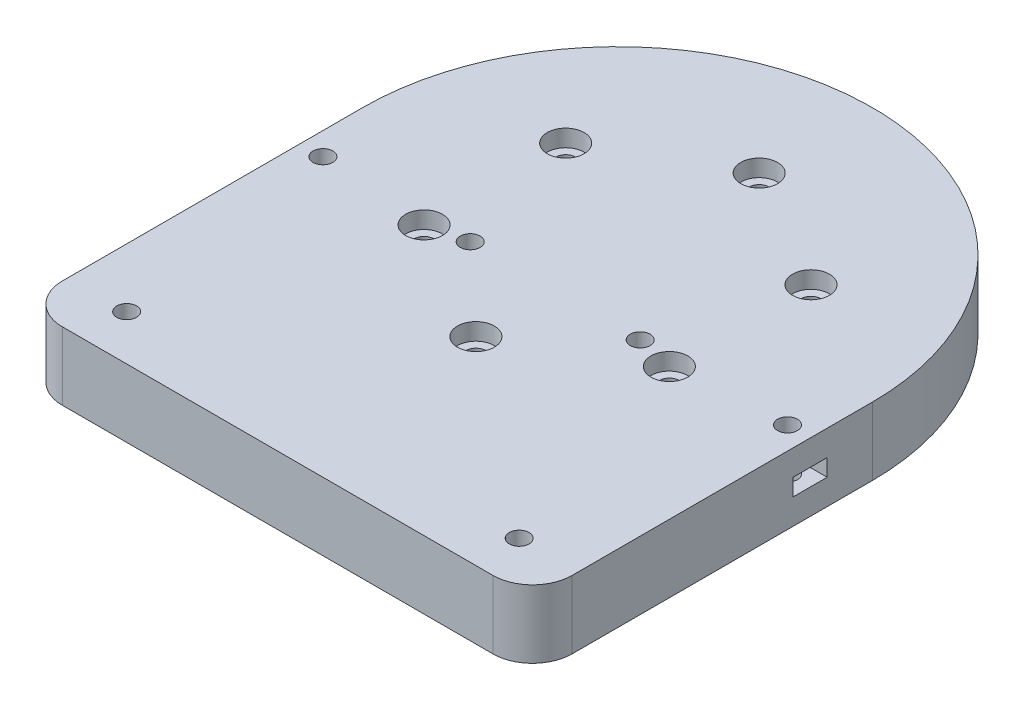
SolidWorks part; units mm, degrees
ref_plane "Front Plane" through (0, 0, 0) normal (0, 0, 1) x (1, 0, 0)
ref_plane "Top Plane" through (0, 0, 0) normal (0, 1, 0) x (1, 0, 0)
ref_plane "Right Plane" through (0, 0, 0) normal (1, 0, 0) x (0, 0, -1)
sketch "Sketch1" plane through (0, 0, 0) normal (0, 1, 0) x (1, 0, 0)
  circle A0 centre (0, 0) radius 45
  dimension "D1" = 90
extrude "Boss-Extrude1" add sketch "Sketch1" along normal blind 12
sketch "Sketch2" plane through (0, 0, 0) normal (0, -1, 0) x (1, 0, 0)
  circle A0 centre (0, 0) radius 35
  dimension "D1" = 70
extrude "Cut-Extrude1" cut sketch "Sketch2" against normal blind 6
sketch "Sketch3" plane through (0, 12, 0) normal (0, 1, 0) x (1, 0, 0)
  line L0 (0, 0) -> (0, -25) construction
  circle A0 centre (0, 0) radius 25 construction
  circle A1 centre (0, -25) radius 1.75
  circle A2 centre (-21.6506, -12.5) radius 1.75
  circle A3 centre (-21.6506, 12.5) radius 1.75
  circle A4 centre (0, 25) radius 1.75
  circle A5 centre (21.6506, 12.5) radius 1.75
  circle A6 centre (21.6506, -12.5) radius 1.75
  point P17 (0, 0)
  dimension "D1" = 50
  dimension "D2" = 3.5
  dimension "D3" = 6
extrude "Cut-Extrude2" cut sketch "Sketch3" against normal through all
sketch "Sketch4" plane through (0, 12, 0) normal (0, 1, 0) x (1, 0, 0)
  circle A0 centre (0, 25) radius 3.25
  circle A1 centre (21.6506, 12.5) radius 3.25
  circle A2 centre (21.6506, -12.5) radius 3.25
  circle A3 centre (0, -25) radius 3.25
  circle A4 centre (-21.6506, -12.5) radius 3.25
  circle A5 centre (-21.6506, 12.5) radius 3.25
  point P15 (0, 0)
  dimension "D1" = 6.5
  dimension "D2" = 6
extrude "Cut-Extrude3" cut sketch "Sketch4" against normal blind 3
sketch "Sketch5" plane through (0, 12, 0) normal (0, 1, 0) x (1, 0, 0)
  line L0 (-45, 0) -> (45, 0) construction
  line L1 (0, 0) -> (0, -45) construction
  line L2 (-45, -11) -> (45, -11) construction
  line L3 (-45, -52) -> (45, -52) construction
  line L4 (-15, -45) -> (-15, 0) construction
  line L5 (-41, -45) -> (-41, 0) construction
  line L6 (-34.64, -52) -> (-34.64, 0) construction
  line L7 (-45, 0) -> (-45, -53)
  line L8 (-38, -60) -> (38, -60)
  line L9 (45, -53) -> (45, 0)
  circle A0 centre (0, 0) radius 45 construction
  arc A1 (-45, 0) -> (45, 0) centre (0, 0) ccw
  arc A2 (38, -60) -> (45, -53) centre (38, -53) ccw
  arc A3 (-45, -53) -> (-38, -60) centre (-38, -53) ccw
  circle M14 centre (0, 0) radius 45
  dimension "D7" = 7
  dimension "D1" = 11
  dimension "D2" = 52
  dimension "D3" = 15
  dimension "D4" = 41
  dimension "D5" = 34.64
  dimension "D6" = 60
extrude "Boss-Extrude3" add sketch "Sketch5" against normal blind 12 contours L7 A3 L8 A2 L9 M14 region at (0, 12, 45.5033)
sketch "Sketch7" plane through (0, 12, 0) normal (0, 1, 0) x (1, 0, 0)
  line L0 (0, 0) -> (0, -60) construction
  line L1 (-38, -60) -> (38, -60) construction
  line L2 (-45, 0) -> (45, 0) construction
  line L3 (-45, 0) -> (-45, -53) construction
  line L4 (-45, -11) -> (45, -11) construction
  line L5 (45, -53) -> (45, 0) construction
  line L6 (-45, -52) -> (45, -52) construction
  line L7 (-41, 0) -> (-41, -60) construction
  line L8 (-15, 0) -> (-15, -60) construction
  line L9 (-34.64, 0) -> (-34.64, -60) construction
  arc A0 (45, 0) -> (-45, 0) centre (0, 0) ccw construction
  circle A1 centre (-34.64, -52) radius 1.75
  circle A2 centre (-41, -11) radius 1.75
  circle A3 centre (-15, -11) radius 1.75
  circle A4 centre (34.64, -52) radius 1.75
  circle A5 centre (15, -11) radius 1.75
  circle A6 centre (41, -11) radius 1.75
  dimension "D6" = 3.5
  dimension "D7" = 3.5
  dimension "D8" = 3.5
  dimension "D1" = 11
  dimension "D2" = 52
  dimension "D3" = 15
  dimension "D4" = 41
  dimension "D5" = 34.64
extrude "Cut-Extrude4" cut sketch "Sketch7" against normal through all
sketch "Sketch8" plane through (0, 6, 0) normal (0, -1, 0) x (1, 0, 0)
  line L0 (21.6506, 12.5) -> (15, 11) construction
  line L1 (0, 0) -> (0, 25) construction
  line L2 (15, 11) -> (13.6049, 17.1855) construction
  line L3 (14.2378, 14.3792) -> (11.6924, 12.0296)
  line L4 (11.6924, 12.0296) -> (12.4546, 8.6503)
  line L5 (12.4546, 8.6503) -> (15.7622, 7.6208)
  line L6 (15.7622, 7.6208) -> (18.3076, 9.9704)
  line L7 (18.3076, 9.9704) -> (17.5454, 13.3497)
  line L8 (17.5454, 13.3497) -> (14.2378, 14.3792)
  line L9 (-18.3076, 9.9704) -> (-17.5454, 13.3497)
  line L10 (-17.5454, 13.3497) -> (-14.2378, 14.3792)
  line L11 (-14.2378, 14.3792) -> (-11.6924, 12.0296)
  line L12 (-11.6924, 12.0296) -> (-12.4546, 8.6503)
  line L13 (-12.4546, 8.6503) -> (-15.7622, 7.6208)
  line L14 (-15.7622, 7.6208) -> (-18.3076, 9.9704)
  circle A0 centre (15, 11) radius 3 construction
  dimension "D2" = 6
  dimension "D1" = 90
extrude "Cut-Extrude5" cut sketch "Sketch8" against normal blind 3
ref_plane "Plane1" through (0, 6, 0) normal (0, -1, 0) x (-1, 0, 0)
sketch "Sketch9" plane through (0, 6, 0) normal (0, -1, 0) x (-1, 0, 0)
  line L0 (0, 0) -> (0, 35) construction
  line L1 (-41, -11) -> (41, -11) construction
  line L2 (-45, -6.0751) -> (-45, -15.3403) construction
  line L3 (-37.5359, -11) -> (-39.2679, -8)
  line L4 (-39.2679, -8) -> (-45, -8)
  line L5 (45, -14) -> (45.0012, -13.9528)
  line L6 (45, -8) -> (45, -14)
  line L7 (-45, -14) -> (-39.2679, -14)
  line L8 (-39.2679, -14) -> (-37.5359, -11)
  line L9 (-45, -53) -> (-45, 0) construction
  line L10 (-45, -8) -> (-45, -14)
  line L11 (-45, -14) -> (-45.0012, -13.9528)
  line L12 (-43.5981, -9.5) -> (-44.4641, -11) [skipped]
  line L13 (-43.5981, -12.5) -> (-42.7321, -14) [skipped]
  line L14 (39.2679, -14) -> (37.5359, -11)
  line L15 (45, -14) -> (39.2679, -14)
  line L16 (39.2679, -8) -> (45, -8)
  line L17 (37.5359, -11) -> (39.2679, -8)
  circle A0 centre (0, 0) radius 35 construction
  circle A1 centre (-41, -11) radius 3 construction
  dimension "D1" = 6
extrude "Cut-Extrude6" cut sketch "Sketch9" against normal blind 1.5 and the other way blind 1.5 contours L4 L10 L7 L8 L3 | L17 L14 L15 L6 L16 region at (41.682, 6, 11) region at (-41.682, 6, 11)
sketch "Sketch10" plane through (0, 0, 0) normal (0, -1, 0) x (1, 0, 0)
  line L0 (34.64, 52) -> (-34.64, 52) construction
  line L1 (0, 52) -> (0, 0) construction
  line L2 (31.1759, 52) -> (32.9079, 49)
  line L3 (32.9079, 49) -> (36.3721, 49)
  line L4 (36.3721, 49) -> (38.1041, 52)
  line L5 (38.1041, 52) -> (36.3721, 55)
  line L6 (36.3721, 55) -> (32.9079, 55)
  line L7 (32.9079, 55) -> (31.1759, 52)
  line L8 (-32.9079, 55) -> (-31.1759, 52)
  line L9 (-36.3721, 55) -> (-32.9079, 55)
  line L10 (-38.1041, 52) -> (-36.3721, 55)
  line L11 (-36.3721, 49) -> (-38.1041, 52)
  line L12 (-32.9079, 49) -> (-36.3721, 49)
  line L13 (-31.1759, 52) -> (-32.9079, 49)
  circle A0 centre (34.64, 52) radius 3 construction
  dimension "D1" = 6
extrude "Cut-Extrude7" cut sketch "Sketch10" against normal blind 6
